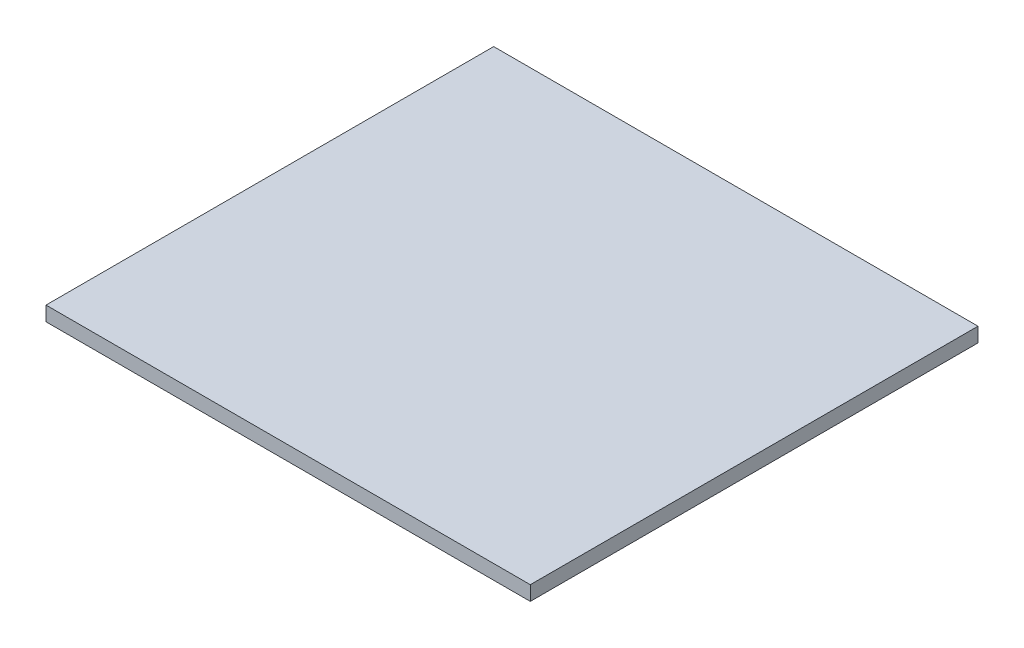
SolidWorks part; units mm, degrees
ref_plane "Front Plane" through (0, 0, 0) normal (0, 0, 1) x (1, 0, 0)
ref_plane "Top Plane" through (0, 0, 0) normal (0, 1, 0) x (1, 0, 0)
ref_plane "Right Plane" through (0, 0, 0) normal (1, 0, 0) x (0, 0, -1)
sketch "Sketch1" plane through (0, 0, 0) normal (0, 1, 0) x (1, 0, 0)
  line L1 (-44.2815, 20.698) -> (62.5985, 20.698)
  line L2 (-44.2815, 20.698) -> (-44.2815, -78.102)
  line L3 (-44.2815, -78.102) -> (62.5985, -78.102)
  line L4 (62.5985, 20.698) -> (62.5985, -78.102)
  dimension "D1" = 106.88
  dimension "D2" = 98.8
extrude "Boss-Extrude1" add sketch "Sketch1" along normal blind 3.2
equation "\"Fit\"= 1"
equation "\"cover width\"= 98.8"
equation "\"bottom 6 length\"= 106.88"
equation "\"thinner acrylic\"= 3.2"
equation "\"D1@Sketch1\"=\"bottom 6 length\""
equation "\"D2@Sketch1\"=\"cover width\""
equation "\"D1@Boss-Extrude1\"=\"thinner acrylic\""
